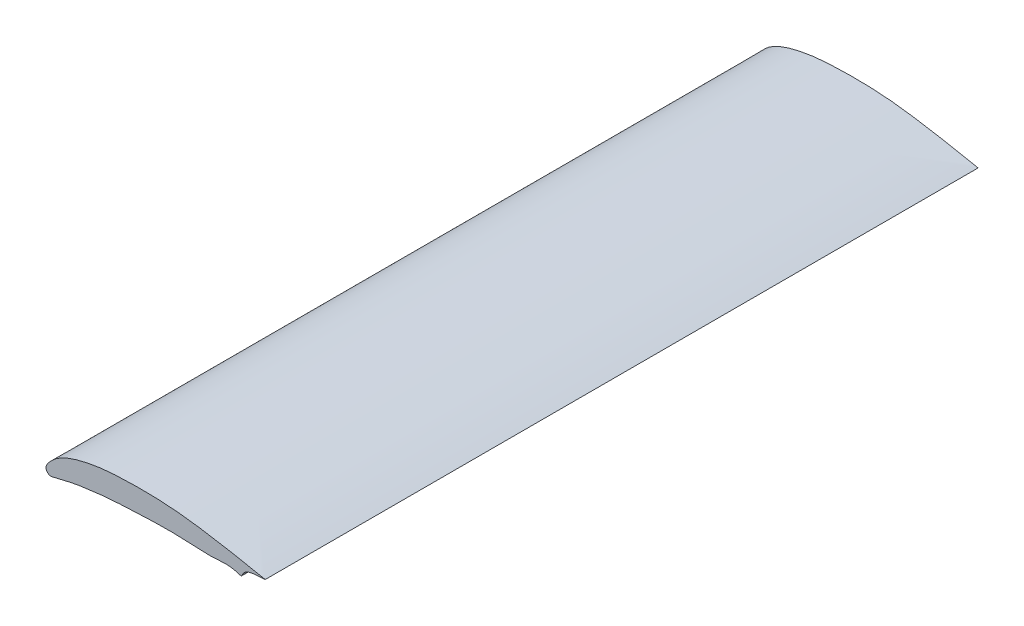
SolidWorks part; units mm, degrees
ref_plane "Front Plane" through (0, 0, 0) normal (0, 0, 1) x (1, 0, 0)
ref_plane "Top Plane" through (0, 0, 0) normal (0, 1, 0) x (1, 0, 0)
ref_plane "Right Plane" through (0, 0, 0) normal (1, 0, 0) x (0, 0, -1)
curve "cut"
  spline degree 3 poles (23.4129, 1.6732, 0) (26.2385, 1.4563, 0) (24.6666, 1.7296, 0) (24.0631, 1.8554, 0) (23.3676, 1.991, 0) (21.8468, 2.2963, 0) (19.449, 2.7181, 0) (16.2072, 3.2214, 0) (12.9484, 3.4695, 0) (9.6969, 3.4728, 0) (6.9821, 3.3475, 0) (4.8205, 2.9999, 0) (3.4681, 2.6661, 0) (2.3898, 2.2791, 0) (1.5621, 1.8808, 0) (0.8771, 1.387, 0) (0.3211, 0.7955, 0) (-0.2215, 0.1147, 0) (0.3268, -0.5439, 0) (0.9664, -0.4072, 0) (1.6227, -0.2531, 0) (2.4342, -0.0542, 0) (3.5055, 0.1899, 0) (4.8628, 0.367, 0) (7.0187, 0.6467, 0) (9.7247, 0.7989, 0) (12.9785, 0.9423, 0) (16.1932, 0.9351, 0) (19.4533, 0.6426, 0) (21.3272, 1.0151, 0) (22.681, 0.4934, 0) (22.872, 0.9133, 0) (23.4129, 1.6732, 0) (26.2385, 1.4563, 0) (24.6666, 1.7296, 0) knots -0.057358 -0.055858 -0.038892 0 0.013065 0.026125 0.039194 0.052259 0.114884 0.177154 0.238899 0.300426 0.362024 0.393129 0.424785 0.441092 0.458148 0.477061 0.488021 0.506046 0.517777 0.525474 0.541223 0.556994 0.572703 0.603759 0.634701 0.696322 0.75786 0.819389 0.880956 0.936472 0.942642 0.944142 0.961108 1 1.013065 1.026125 1.039194 periodic
sketch "cut sketch" plane through (0, 0, 0) normal (0, 0, 1) x (1, 0, 0)
  line L0 (0, 0) -> (19.8755, 0) construction
  line L1 (19.8755, 0) -> (19.8755, 1.2434) construction
  line L2 (9.9377, 0) -> (9.9377, 2.69) construction
  line L3 (198.755, 0) -> (198.755, 12.4341) construction
  line L4 (0, 0) -> (198.755, 0) construction
  line L5 (99.3775, 0) -> (99.3775, 26.9) construction
  line L6 (50.8, 0) -> (50.8, 4.4202) construction
  line L7 (50.8, 4.4202) -> (50.8, 25.4008) construction
  line L8 (101.6, 0) -> (101.6, 7.179) construction
  line L9 (101.6, 7.179) -> (101.6, 26.8197) construction
  circle A0 centre (50.8, 14.9105) radius 7.9375
  circle A1 centre (101.6, 16.9993) radius 7.9375
  spline S0 degree 3 poles (183.2058, 13.0927) (205.3166, 11.3957) (193.0163, 13.5342) (188.2941, 14.5185) (182.8517, 15.5792) (170.9511, 17.9689) (152.1886, 21.2695) (126.8211, 25.2077) (101.3214, 27.1488) (75.8786, 27.1749) (54.6349, 26.194) (37.7206, 23.4738) (27.1378, 20.8625) (18.6998, 17.8336) (12.2233, 14.7175) (6.8632, 10.853) (2.5126, 6.2248) (-1.7331, 0.8973) (2.5575, -4.2564) (7.562, -3.1865) (12.6976, -1.9802) (19.0475, -0.4243) (27.4305, 1.4859) (38.0511, 2.872) (54.9212, 5.0608) (76.096, 6.2515) (101.5566, 7.3732) (126.7117, 7.3174) (152.222, 5.0287) (166.8852, 7.9435) (177.4789, 3.8608) (178.9732, 7.1462) (183.2058, 13.0927) (205.3166, 11.3957) (193.0163, 13.5342) knots -0.057358 -0.055858 -0.038892 0 0.013065 0.026125 0.039194 0.052259 0.114884 0.177154 0.238899 0.300426 0.362024 0.393129 0.424785 0.441092 0.458148 0.477061 0.488021 0.506046 0.517777 0.525474 0.541223 0.556994 0.572703 0.603759 0.634701 0.696322 0.75786 0.819389 0.880956 0.936472 0.942642 0.944142 0.961108 1 1.013065 1.026125 1.039194 only from (198.755, 12.4341) to (198.755, 12.4341)
  spline S2 degree 3 poles (18.3206, 1.3093) (20.5317, 1.1396) (19.3016, 1.3534) (18.8294, 1.4518) (18.2852, 1.5579) (17.0951, 1.7969) (15.2189, 2.1269) (12.6821, 2.5208) (10.1321, 2.7149) (7.5879, 2.7175) (5.4635, 2.6194) (3.7721, 2.3474) (2.7138, 2.0862) (1.87, 1.7834) (1.2223, 1.4718) (0.6863, 1.0853) (0.2513, 0.6225) (-0.1733, 0.0897) (0.2558, -0.4256) (0.7562, -0.3186) (1.2698, -0.198) (1.9047, -0.0424) (2.743, 0.1486) (3.8051, 0.2872) (5.4921, 0.5061) (7.6096, 0.6252) (10.1557, 0.7373) (12.6712, 0.7317) (15.2222, 0.5029) (16.6885, 0.7944) (17.7479, 0.3861) (17.8973, 0.7146) (18.3206, 1.3093) (20.5317, 1.1396) (19.3016, 1.3534) knots -0.057358 -0.055858 -0.038892 0 0.013065 0.026125 0.039194 0.052259 0.114884 0.177154 0.238899 0.300426 0.362024 0.393129 0.424785 0.441092 0.458148 0.477061 0.488021 0.506046 0.517777 0.525474 0.541223 0.556994 0.572703 0.603759 0.634701 0.696322 0.75786 0.819389 0.880956 0.936472 0.942642 0.944142 0.961108 1 1.013065 1.026125 1.039194 only from (19.8755, 1.2434) to (19.8755, 1.2434) construction
  point P11 (50.8, 0)
  point P17 (101.6, 0)
  point P20 (101.6, 16.9993)
  dimension "D8" = 15.875
  dimension "D10" = 15.875
  dimension "D1" = 1.2434
  dimension "D2" = 19.8755
  dimension "D3" = 2.69
  dimension "D4" = 198.755
  dimension "D5" = 12.4341
  dimension "D6" = 26.9
  dimension "D7" = 50.8
  dimension "D9" = 50.8
curve "full"
  spline degree 3 poles (25.4, 0.0889, 0) (24.9755, 0.1879, 0) (24.1284, 0.3854, 0) (22.4316, 0.7474, 0) (20.3056, 1.1527, 0) (17.7661, 1.6728, 0) (15.2225, 2.1285, 0) (12.6828, 2.5208, 0) (10.1333, 2.7153, 0) (7.5886, 2.7177, 0) (5.4641, 2.6194, 0) (3.7724, 2.3478, 0) (2.7142, 2.0863, 0) (1.8702, 1.7836, 0) (1.2225, 1.4719, 0) (0.6864, 1.0854, 0) (0.2512, 0.6226, 0) (-0.1733, 0.0898, 0) (0.2557, -0.4257, 0) (0.7562, -0.3188, 0) (1.2698, -0.1979, 0) (1.905, -0.0426, 0) (2.7433, 0.1487, 0) (3.8055, 0.2872, 0) (5.4925, 0.5064, 0) (7.6119, 0.6227, 0) (10.1512, 0.7472, 0) (12.6929, 0.6952, 0) (15.2354, 0.6324, 0) (17.7755, 0.4534, 0) (20.3173, 0.2785, 0) (22.4335, 0.1017, 0) (24.1313, 0.0327, 0) (24.9769, -0.0484, 0) (25.4, -0.0889, 0) knots 0 0 0 0 0.025045 0.049982 0.099693 0.149405 0.198931 0.248178 0.297011 0.345669 0.394384 0.418982 0.444018 0.456913 0.470405 0.485361 0.494029 0.508284 0.517562 0.523649 0.536105 0.548579 0.561002 0.585562 0.610033 0.658766 0.707435 0.756094 0.804785 0.853571 0.902386 0.951201 0.975578 1 1 1 1
sketch "full foil sketch" plane through (0, 0, 0) normal (0, 0, 1) x (1, 0, 0)
  line L0 (25.4, 0.0889) -> (25.4, -0.0889)
  spline S0 degree 3 poles (801.0896, 2896.6153) (93.9918, -50.1126) (62.4745, -7.7955) (22.4316, 0.7474) (20.3056, 1.1527) (17.7661, 1.6728) (15.2225, 2.1285) (12.6828, 2.5208) (10.1333, 2.7153) (7.5886, 2.7177) (5.4641, 2.6194) (3.7724, 2.3478) (2.7142, 2.0863) (1.8702, 1.7836) (1.2225, 1.4719) (0.6864, 1.0854) (0.2512, 0.6226) (-0.1733, 0.0898) (0.2557, -0.4257) (0.7562, -0.3188) (1.2698, -0.1979) (1.905, -0.0426) (2.7433, 0.1487) (3.8055, 0.2872) (5.4925, 0.5064) (7.6119, 0.6227) (10.1512, 0.7472) (12.6929, 0.6952) (15.2354, 0.6324) (17.7755, 0.4534) (20.3173, 0.2785) (22.4335, 0.1017) (51.136, -1.0652) (75.492, -52.2811) (315.1102, 2985.1217) knots -2.25291 -2.25291 -2.25291 -2.25291 0.025045 0.049982 0.099693 0.149405 0.198931 0.248178 0.297011 0.345669 0.394384 0.418982 0.444018 0.456913 0.470405 0.485361 0.494029 0.508284 0.517562 0.523649 0.536105 0.548579 0.561002 0.585562 0.610033 0.658766 0.707435 0.756094 0.804785 0.853571 0.902386 0.951201 0.975578 2.552608 2.552608 2.552608 2.552608 only from (25.4, 0.0889) to (25.4, -0.0889) construction
  spline S1 degree 3 poles (25.4, 0.0889) (24.9755, 0.1879) (24.1284, 0.3854) (22.4316, 0.7474) (20.3056, 1.1527) (17.7661, 1.6728) (15.2225, 2.1285) (12.6828, 2.5208) (10.1333, 2.7153) (7.5886, 2.7177) (5.4641, 2.6194) (3.7724, 2.3478) (2.7142, 2.0863) (1.8702, 1.7836) (1.2225, 1.4719) (0.6864, 1.0854) (0.2512, 0.6226) (-0.1733, 0.0898) (0.2557, -0.4257) (0.7562, -0.3188) (1.2698, -0.1979) (1.905, -0.0426) (2.7433, 0.1487) (3.8055, 0.2872) (5.4925, 0.5064) (7.6119, 0.6227) (10.1512, 0.7472) (12.6929, 0.6952) (15.2354, 0.6324) (17.7755, 0.4534) (20.3173, 0.2785) (22.4335, 0.1017) (24.1313, 0.0327) (24.9769, -0.0484) (25.4, -0.0889) knots 0 0 0 0 0.025045 0.049982 0.099693 0.149405 0.198931 0.248178 0.297011 0.345669 0.394384 0.418982 0.444018 0.456913 0.470405 0.485361 0.494029 0.508284 0.517562 0.523649 0.536105 0.548579 0.561002 0.585562 0.610033 0.658766 0.707435 0.756094 0.804785 0.853571 0.902386 0.951201 0.975578 1 1 1 1
extrude "Boss-Extrude1" add sketch "cut sketch" along normal blind 647.7 contours S0 A0 A1 | A0 | A1 region at (50.8, 14.9105, 0) region at (101.6, 16.9993, 0) region at (89.2313, 14.6074, 0)
ref_plane "Plane1" through (0, 0, 323.85) normal (0, 0, 1) x (1, 0, 0)
sketch "Sketch1" plane through (0, 0, 323.85) normal (0, 0, 1) x (1, 0, 0)
  line L0 (177.1106, 4.2496) -> (177.1106, -23.538) construction
  line L1 (177.1106, -23.538) -> (184.7306, -23.538) construction
  circle A0 centre (184.7306, -23.538) radius 1.27
  point P0 (177.1106, 4.2496)
  point P6 (177.1106, 4.2496)
  dimension "D3" = 2.54
  dimension "D1" = 27.7876
  dimension "D2" = 7.62
ref_plane "Plane2" through (0, 0, 0) normal (0, -1, 0) x (1, 0, 0)
